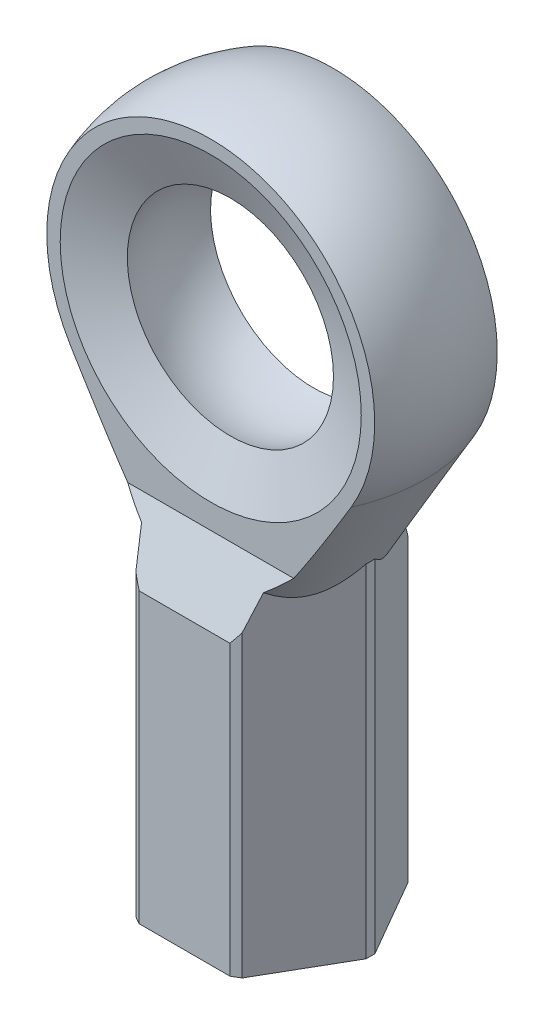
SolidWorks part; units mm, degrees
ref_plane "Front Plane" through (0, 0, 0) normal (0, 0, 1) x (1, 0, 0)
ref_plane "Top Plane" through (0, 0, 0) normal (0, 1, 0) x (1, 0, 0)
ref_plane "Right Plane" through (0, 0, 0) normal (1, 0, 0) x (0, 0, -1)
ref_plane "Plane1" through (0, 0, 0) normal (0, 1, 0) x (1, 0, 0)
sketch "Sketch1" plane through (0, 0, 0) normal (0, 1, 0) x (1, 0, 0)
  line L0 (-5.624, -0.2589) -> (-3.0362, -4.7411)
  line L1 (-2.5878, -5) -> (2.5878, -5)
  line L2 (3.0362, -4.7411) -> (5.624, -0.2589)
  line L3 (5.624, 0.2589) -> (3.0362, 4.7411)
  line L4 (2.5878, 5) -> (-2.5878, 5)
  line L5 (-3.0362, 4.7411) -> (-5.624, 0.2589)
  arc A0 (-5.624, 0.2589) -> (-5.624, -0.2589) centre (0, 0) ccw
  arc A1 (-3.0362, -4.7411) -> (-2.5878, -5) centre (0, 0) ccw
  arc A2 (2.5878, -5) -> (3.0362, -4.7411) centre (0, 0) ccw
  arc A3 (5.624, -0.2589) -> (5.624, 0.2589) centre (0, 0) ccw
  arc A4 (3.0362, 4.7411) -> (2.5878, 5) centre (0, 0) ccw
  arc A5 (-2.5878, 5) -> (-3.0362, 4.7411) centre (0, 0) ccw
extrude "Boss-Extrude1" add sketch "Sketch1" along normal blind 30
ref_plane "Plane2" through (0, 0, 0) normal (0, 0, 1) x (1, 0, 0)
sketch "Sketch2" plane through (0, 0, 0) normal (0, 0, 1) x (1, 0, 0)
  line L0 (8.7462, 25.1519) -> (0, 9.3733)
  line L1 (0, 9.3733) -> (0, 40)
  line L2 (0, 9.3733) -> (0, 40) construction
  arc A0 (0, 40) -> (8.7462, 25.1519) centre (0, 30) cw
revolve "Revolve1" add sketch "Sketch2" angle 360 about L2 reverse direction yes
ref_plane "Plane3" through (0, 0, 0) normal (1, 0, 0) x (0, 0, -1)
sketch "Sketch3" plane through (0, 0, 0) normal (1, 0, 0) x (0, 0, -1)
  line L0 (-11, 10) -> (-7.7467, 10)
  line L1 (-7.7467, 10) -> (-3.5, 20.0045)
  line L2 (-3.5, 20.0045) -> (-3.5, 40)
  line L3 (-3.5, 40) -> (3.5, 40)
  line L4 (3.5, 40) -> (3.5, 20.0045)
  line L5 (3.5, 20.0045) -> (7.7467, 10)
  line L6 (7.7467, 10) -> (11, 10)
  line L7 (11, 10) -> (11, 50)
  line L8 (11, 50) -> (-11, 50)
  line L9 (-11, 50) -> (-11, 10)
extrude "Cut-Extrude1" cut sketch "Sketch3" against normal blind 11 and the other way blind 11
ref_plane "Plane4" through (0, 0, 0) normal (0, 0, 1) x (1, 0, 0)
sketch "Sketch4" plane through (0, 0, 0) normal (0, 0, 1) x (1, 0, 0)
  line L0 (0, 14.9194) -> (2.4585, 13.5)
  line L1 (2.4585, 13.5) -> (2.4585, 0.5415)
  line L2 (2.4585, 0.5415) -> (3, 0)
  line L3 (3, 0) -> (0, 0)
  line L4 (0, 0) -> (0, 14.9194)
  line L5 (0, 0) -> (0, 14.9194) construction
revolve "Cut-Revolve1" cut sketch "Sketch4" angle 360 about L5 reverse direction yes
cosmetic thread "Cosmetic Thread1" parameters "D1"=13.5, "D2"=6
ref_plane "Plane5" through (0, 0, 0) normal (1, 0, 0) x (0, 0, -1)
sketch "Sketch5" plane through (0, 0, 0) normal (1, 0, 0) x (0, 0, -1)
  line L0 (-4.5, 30) -> (-4.5, 38.6)
  line L1 (-4.5, 38.6) -> (-3.5, 38.6)
  line L2 (-3.5, 38.6) -> (-2.3768, 35.8884)
  line L3 (2.3768, 35.8884) -> (3.5, 38.6)
  line L4 (3.5, 38.6) -> (4.5, 38.6)
  line L5 (4.5, 38.6) -> (4.5, 30)
  line L6 (4.5, 30) -> (-4.5, 30)
  line L7 (4.5, 30) -> (-4.5, 30) construction
  arc A0 (-2.3768, 35.8884) -> (2.3768, 35.8884) centre (0, 30) cw
revolve "Cut-Revolve2" cut sketch "Sketch5" angle 360 about L7 reverse direction yes
sketch "Sketch6" plane through (0, 0, 0) normal (0, 0, 1) x (1, 0, 0)
  point P0 (0, 30)
